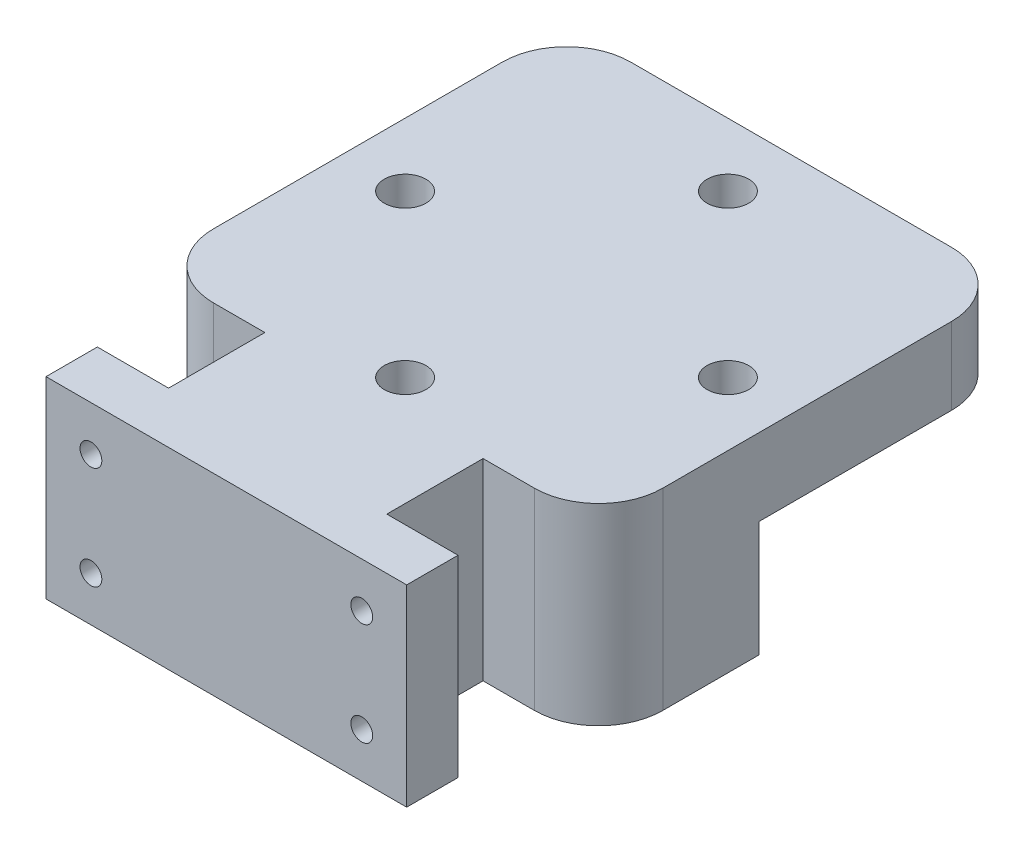
SolidWorks part; units mm, degrees
ref_plane "Front Plane" through (0, 0, 0) normal (0, 0, 1) x (1, 0, 0)
ref_plane "Top Plane" through (0, 0, 0) normal (0, 1, 0) x (1, 0, 0)
ref_plane "Right Plane" through (0, 0, 0) normal (1, 0, 0) x (0, 0, -1)
sketch "Sketch1" plane through (0, 0, 0) normal (0, 0, 1) x (1, 0, 0)
  line L0 (0, 0) -> (56.2, 0)
  line L1 (28.1, -5.5) -> (28.1, -10) construction
  line L2 (0, 0) -> (0, -30)
  line L3 (0, -30) -> (56.2, -30)
  line L5 (56.2, 0) -> (56.2, -30)
  line L8 (35.8259, -3) -> (37.9889, -3) construction
  line L18 (0, -15) -> (56.2, -15) construction
  arc A0 (19.5099, 0) -> (37.9889, -3) centre (28.1, -5.5) ccw construction
  arc A1 (35.8259, 0) -> (35.8259, -3) centre (35.8259, -1.5) ccw construction
  dimension "D4" = 30
  dimension "D5" = 1.5
  dimension "D1" = 10.2
  dimension "D3" = 56.2
extrude "Boss-Extrude1" add sketch "Sketch1" along normal blind 5
sketch "Sketch3" plane through (0, 0, 5) normal (0, 0, 1) x (1, 0, 0)
  line L0 (0, 0) -> (0, -30)
  line L1 (0, -30) -> (56.2, -30)
  line L2 (56.2, -30) -> (56.2, 0) construction
  line L3 (0, 0) -> (56.2, 0)
  line L4 (56.2, 0) -> (56.2, -30)
extrude "Boss-Extrude2" add sketch "Sketch3" along normal blind 3
sketch "Sketch4" plane through (0, 0, 0) normal (0, 0, -1) x (-1, 0, 0)
  line L0 (-56.2, -15) -> (0, -15) construction
  line L1 (-56.2, -30) -> (-56.2, 0) construction
  line L2 (0, 0) -> (0, -30) construction
  circle A0 centre (-49.2, -7) radius 1.7
  circle A1 centre (-7, -7) radius 1.7
  circle A2 centre (-7, -23) radius 1.7
  circle A3 centre (-49.2, -23) radius 1.7
  dimension "D1" = 3.4
  dimension "D2" = 49.2
  dimension "D3" = 7
extrude "Cut-Extrude2" cut sketch "Sketch4" against normal up to surface (8 mm away) up to face at (28.1, -15, 8)
sketch "Sketch5" plane through (0, 0, 0) normal (0, 1, 0) x (1, 0, 0)
  line L0 (0, 0) -> (7, 0) construction
  line L1 (56.2, 0) -> (0, 0) construction
  line L2 (7, 0) -> (8.7, 0) construction
  line L3 (8.7, 0) -> (11.7, 0) construction
  line L4 (28.1, 0) -> (28.1, -8) construction
  line L5 (56.2, -8) -> (0, -8) construction
  line L6 (44.5, 0) -> (11.7, 0)
  line L7 (11.7, 0) -> (11.7, 15)
  line L10 (11.7, 15) -> (-8.3, 15)
  line L11 (-8.3, 15) -> (-8.3, 65)
  line L12 (-3.3, 70) -> (59.5, 70)
  line L13 (44.5, 0) -> (44.5, 15)
  line L14 (64.5, 15) -> (64.5, 65)
  line L15 (44.5, 15) -> (64.5, 15)
  arc A2 (-8.3, 65) -> (-3.3, 70) centre (-3.3, 65) cw
  arc A3 (64.5, 65) -> (59.5, 70) centre (59.5, 65) ccw
  point P17 (-8.3, 70)
  point P24 (28.1, 70)
  point P25 (64.5, 70)
  dimension "D5" = 20
  dimension "D7" = 5
  dimension "D1" = 7
  dimension "D2" = 1.7
  dimension "D3" = 3
  dimension "D4" = 15
  dimension "D6" = 55
extrude "Boss-Extrude3" [suppressed] add sketch "Sketch5" against normal blind 12
ref_plane "Plane1" through (28.1, 0, 0) normal (1, 0, 0) x (0, 0, -1)
sketch "Sketch6" [suppressed] plane through (28.1, 0, 0) normal (1, 0, 0) x (0, 0, -1)
  line L4 (0, -12) -> (0, -30)
  line L5 (0, -12) -> (15, -12) construction
  line L6 (0, -30) -> (70, -12)
  line L7 (70, -12) -> (0, -12)
extrude "Boss-Extrude4" [suppressed] add sketch "Sketch6" along normal blind 10 and the other way blind 10
sketch "Sketch7" [suppressed] plane through (28.1, 0, 0) normal (1, 0, 0) x (0, 0, -1)
  line L0 (8, -12) -> (8, -22)
  line L1 (70, -12) -> (0, -12) construction
  line L3 (8, -12) -> (46.8889, -12)
  line L5 (8, -22) -> (46.8889, -12)
  line L6 (0, -30) -> (70, -12) construction
  dimension "D1" = 8
  dimension "D2" = 10
  dimension "D3" = 38.8889
extrude "Cut-Extrude3" [suppressed] cut sketch "Sketch7" against normal up to next and the other way up to next
sketch "Sketch8" plane through (0, 0, 0) normal (0, 0, -1) x (-1, 0, 0)
  line L3 (-56.2, -15) -> (0, -15) construction
  line L4 (-56.2, -30) -> (-56.2, 0) construction
  line L5 (0, 0) -> (0, -30) construction
  circle A0 centre (-49.2, -7) radius 2.6
  circle A1 centre (-7, -7) radius 2.6
  circle A2 centre (-7, -23) radius 2.6
  circle A3 centre (-49.2, -23) radius 2.6
  dimension "D1" = 5.2
extrude "Cut-Extrude4" cut sketch "Sketch8" against normal blind 4
sketch "Sketch9" plane through (28.1, 0, 0) normal (1, 0, 0) x (0, 0, -1)
  line L0 (0, 0) -> (0, -7) construction
  line L1 (-8, -15) -> (0, -15) construction
  line L2 (-8, -30) -> (-8, 0) construction
  line L3 (0, -30) -> (0, 0) construction
  line L4 (0, -7) -> (0, -9.6) construction
  line L5 (0, -30) -> (0, 0)
  line L6 (0, 0) -> (15, 0)
  line L7 (15, 0) -> (15, -30)
  line L8 (0, -30) -> (15, -30)
  point P14 (15, -15)
  dimension "D1" = 7
  dimension "D2" = 2.6
  dimension "D3" = 15
  dimension "D4" = 15
extrude "Boss-Extrude5" add sketch "Sketch9" along normal blind 17 and the other way blind 17
sketch "Sketch10" plane through (0, 0, 0) normal (0, 1, 0) x (1, 0, 0)
  line L0 (28.1, 15) -> (28.1, 45) construction
  line L1 (11.1, 15) -> (45.1, 15) construction
  line L2 (-1.9, 45) -> (58.1, 45) construction
  line L3 (53.1, 15) -> (3.1, 15)
  line L5 (-6.9, 25) -> (-6.9, 70)
  line L7 (3.1, 80) -> (53.1, 80)
  line L9 (63.1, 25) -> (63.1, 70)
  circle A0 centre (28.1, 45) radius 30 construction
  circle A1 centre (28.1, 70.15) radius 2.2 construction
  circle A2 centre (53.25, 45) radius 2.2 construction
  circle A3 centre (28.1, 19.85) radius 2.2 construction
  circle A4 centre (2.95, 45) radius 2.2 construction
  arc A5 (63.1, 25) -> (53.1, 15) centre (53.1, 25) cw
  arc A6 (63.1, 70) -> (53.1, 80) centre (53.1, 70) ccw
  arc A7 (3.1, 15) -> (-6.9, 25) centre (3.1, 25) cw
  arc A8 (3.1, 80) -> (-6.9, 70) centre (3.1, 70) ccw
  point P15 (28.1, 45)
  point P25 (28.1, 80)
  dimension "D1" = 4.4
  dimension "D5" = 60
  dimension "D7" = 10
  dimension "D2" = 35
  dimension "D3" = 35
extrude "Boss-Extrude6" add sketch "Sketch10" against normal blind 12
sketch "Sketch11" plane through (0, 0, 0) normal (0, 1, 0) x (1, 0, 0)
  line L0 (28.1, 15) -> (28.1, 45) construction
  line L1 (-1.9, 45) -> (58.1, 45) construction
  line L2 (53.1, 15) -> (3.1, 15) construction
  line L3 (-6.9, 25) -> (-6.9, 70) construction
  line L4 (3.1, 80) -> (53.1, 80) construction
  line L5 (63.1, 25) -> (63.1, 70) construction
  circle A0 centre (28.1, 45) radius 30 construction
  circle A1 centre (28.1, 70.15) radius 2.2
  circle A2 centre (53.25, 45) radius 2.2
  circle A3 centre (28.1, 19.85) radius 2.2
  circle A4 centre (2.95, 45) radius 2.2
  arc A5 (63.1, 25) -> (53.1, 15) centre (53.1, 25) cw construction
  arc A6 (63.1, 70) -> (53.1, 80) centre (53.1, 70) ccw construction
  arc A7 (3.1, 15) -> (-6.9, 25) centre (3.1, 25) cw construction
  arc A8 (3.1, 80) -> (-6.9, 70) centre (3.1, 70) ccw construction
  point P13 (28.1, 45)
  point P15 (28.1, 80)
  dimension "D1" = 4.4
  dimension "D2" = 60
  dimension "D3" = 10
  dimension "D4" = 35
  dimension "D5" = 35
extrude "Cut-Extrude5" cut sketch "Sketch11" against normal up to surface (12 mm away) up to face at (28.1, -12, -41)
ref_plane "Plane2" through (0, -12, 0) normal (0, 1, 0) x (1, 0, 0)
sketch "Sketch12" plane through (0, -12, 0) normal (0, 1, 0) x (1, 0, 0)
  line L1 (-1.9, 45) -> (58.1, 45) construction
  line L2 (53.1, 15) -> (3.1, 15) construction
  line L3 (-6.9, 25) -> (-6.9, 70) construction
  line L4 (3.1, 80) -> (53.1, 80) construction
  line L5 (63.1, 25) -> (63.1, 70) construction
  line L6 (28.1, 15) -> (28.1, 13) construction
  line L7 (45.1, 13) -> (11.1, 13)
  line L8 (11.1, 0) -> (11.1, 15) construction
  line L9 (11.1, 13) -> (11.1, 15)
  line L10 (11.1, 15) -> (3.1, 15)
  line L11 (-6.9, 25) -> (-6.9, 40)
  line L12 (-6.9, 40) -> (-2.4941, 40)
  line L13 (63.1, 40) -> (58.6941, 40)
  line L14 (63.1, 25) -> (63.1, 40)
  line L15 (45.1, 15) -> (53.1, 15)
  line L16 (45.1, 13) -> (45.1, 15)
  circle A1 centre (28.1, 70.15) radius 2.2 construction
  circle A2 centre (53.25, 45) radius 2.2 construction
  circle A3 centre (28.1, 19.85) radius 2.2 construction
  circle A4 centre (2.95, 45) radius 2.2 construction
  arc A5 (63.1, 25) -> (53.1, 15) centre (53.1, 25) cw construction
  arc A6 (63.1, 70) -> (53.1, 80) centre (53.1, 70) ccw construction
  arc A7 (3.1, 15) -> (-6.9, 25) centre (3.1, 25) cw construction
  arc A8 (3.1, 80) -> (-6.9, 70) centre (3.1, 70) ccw construction
  arc A9 (-6.9, 25) -> (3.1, 15) centre (3.1, 25) ccw
  arc A10 (63.1, 25) -> (53.1, 15) centre (53.1, 25) cw
  arc A12 (-2.4941, 40) -> (58.6941, 40) centre (28.1, 45) ccw
  point P13 (28.1, 45)
  point P15 (28.1, 80)
  dimension "D1" = 4.4
  dimension "D2" = 62
  dimension "D7" = 10
  dimension "D6" = 2
  dimension "D8" = 15
extrude "Boss-Extrude7" add sketch "Sketch12" against normal up to surface (18 mm away) up to face at (28.1, -30, -1.75)
sketch "Sketch13" plane through (0, -12, 0) normal (0, 1, 0) x (1, 0, 0)
  line L1 (20.2898, 15) -> (35.9102, 15)
  arc A0 (20.2898, 15) -> (35.9102, 15) centre (28.1, 45) ccw
extrude "Cut-Extrude6" cut sketch "Sketch13" against normal up to surface (18 mm away) up to face at (28.1, -30, -15.172)
sketch "Sketch14" plane through (0, 0, 0) normal (0, 1, 0) x (1, 0, 0)
  line L0 (28.1, 70.15) -> (28.1, 19.85) construction
  line L2 (53.25, 45) -> (2.95, 45) construction
  circle A0 centre (28.1, 70.15) radius 3.25
  circle A1 centre (28.1, 45) radius 25.15 construction
  circle A2 centre (53.25, 45) radius 3.25
  circle A3 centre (28.1, 19.85) radius 3.25
  circle A4 centre (2.95, 45) radius 3.25
  point P20 (28.1, 45)
  dimension "D1" = 6.5
  dimension "D2" = 4
extrude "Cut-Extrude7" cut sketch "Sketch14" against normal blind 8
